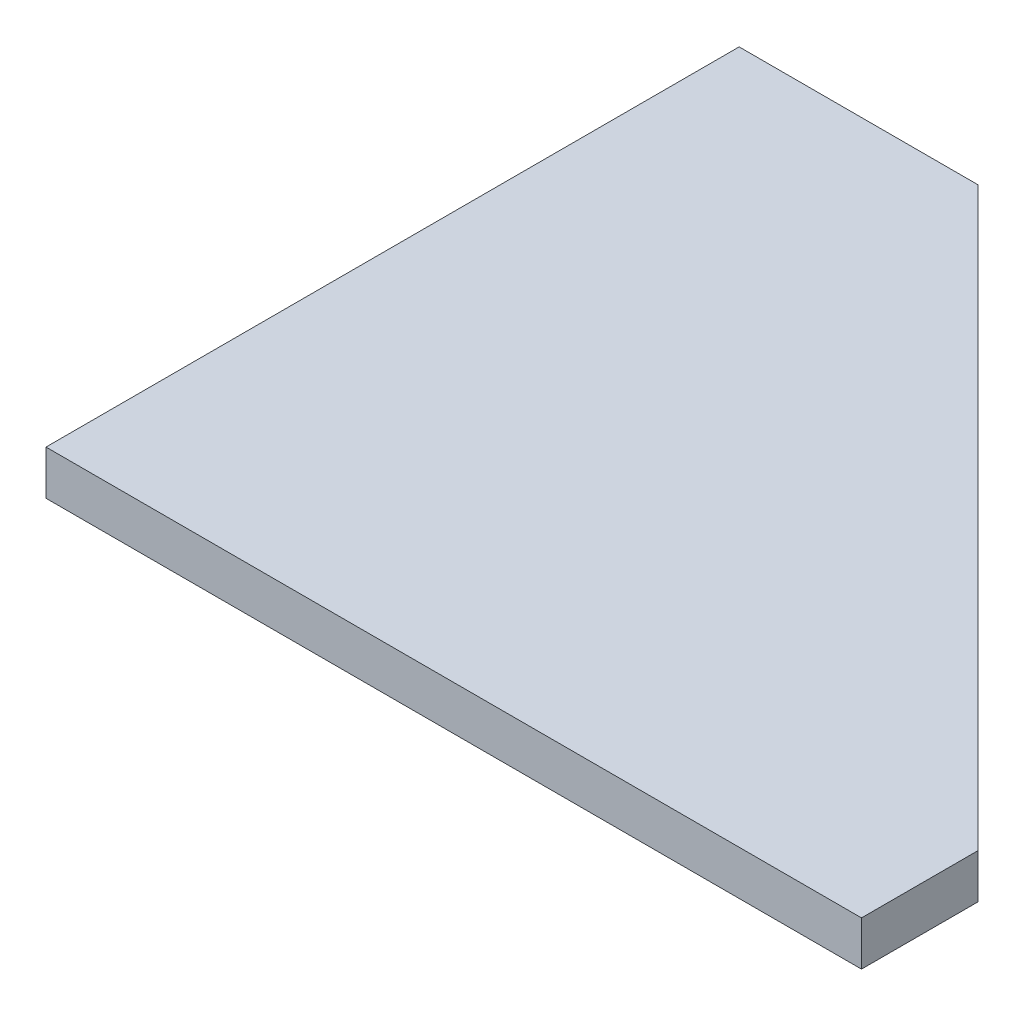
SolidWorks part; units mm, degrees
ref_plane "Front Plane" through (0, 0, 0) normal (0, 0, 1) x (1, 0, 0)
ref_plane "Top Plane" through (0, 0, 0) normal (0, 1, 0) x (1, 0, 0)
ref_plane "Right Plane" through (0, 0, 0) normal (1, 0, 0) x (0, 0, -1)
sketch "Sketch1" plane through (0, 0, 0) normal (0, 1, 0) x (1, 0, 0)
  line L0 (-144.97, 297.485) -> (350, -197.485)
  line L1 (-350, 297.485) -> (-144.97, 297.485)
  line L2 (-350, 297.485) -> (-350, -297.485)
  line L3 (-350, -297.485) -> (350, -297.485)
  line L4 (350, -197.485) -> (350, -297.485)
  line L5 (-350, 297.485) -> (350, -297.485) construction
  point P0 (0, 0)
  dimension "D1" = 594.97
  dimension "D2" = 700
  dimension "D3" = 100
  dimension "D4" = 45
extrude "Boss-Extrude1" add sketch "Sketch1" along normal blind 38.1
